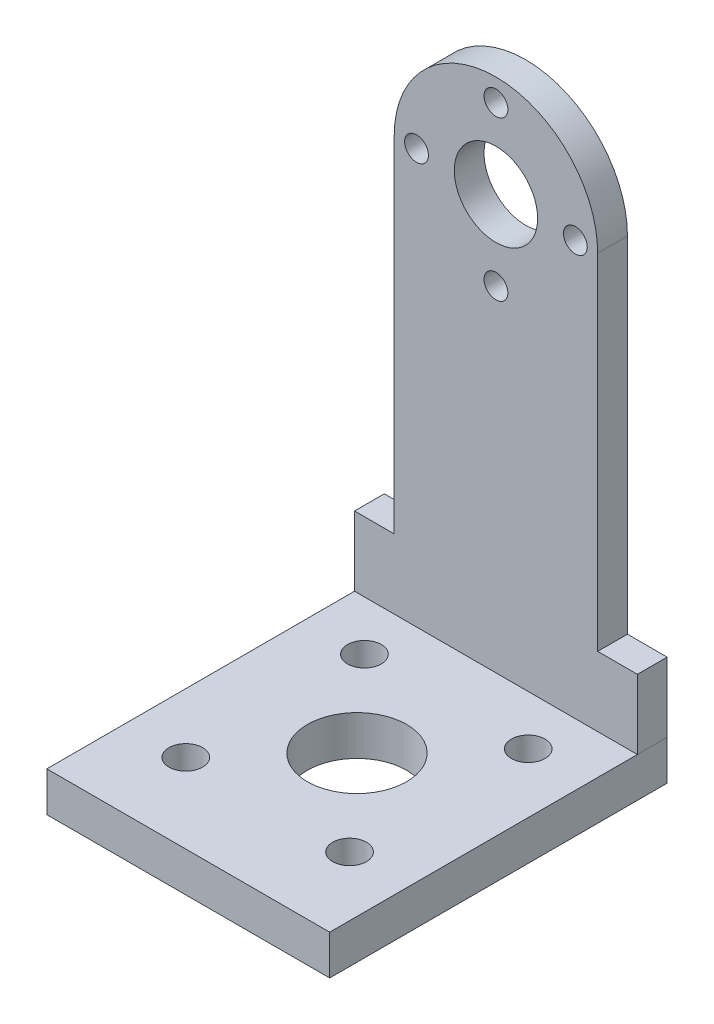
SolidWorks part; units mm, degrees
ref_plane "Front Plane" through (0, 0, 0) normal (0, 0, 1) x (1, 0, 0)
ref_plane "Top Plane" through (0, 0, 0) normal (0, 1, 0) x (1, 0, 0)
ref_plane "Right Plane" through (0, 0, 0) normal (1, 0, 0) x (0, 0, -1)
sketch "Sketch1" plane through (0, 0, 0) normal (0, 0, 1) x (1, 0, 0)
  line L0 (0, 0) -> (0, -100) construction
  line L1 (0, -100) -> (-70, -100) construction
  line L2 (-10.25, -60) -> (-70, -60) construction
  line L4 (-10.25, 0) -> (10.25, 0)
  line L5 (-10.25, 0) -> (-10.25, -60)
  line L7 (10.25, 0) -> (10.25, -60)
  line L8 (-10.25, 0) -> (10.25, 0)
  line L9 (-10.25, 0) -> (-10.25, -100)
  line L10 (-10.25, -100) -> (10.25, -100)
  line L11 (10.25, 0) -> (10.25, -100)
  circle A0 centre (0, 0) radius 10.25
  circle A1 centre (0, 0) radius 8
  circle A2 centre (0, 0) radius 4.2
  circle A3 centre (0, 8) radius 1.2
  circle A4 centre (8, 0) radius 1.2
  circle A5 centre (0, -8) radius 1.2
  circle A6 centre (-8, 0) radius 1.2
  point P16 (0, 0)
  dimension "D1" = 20.5
  dimension "D2" = 16
  dimension "D3" = 8.4
  dimension "D4" = 2.4
  dimension "D6" = 100
  dimension "D7" = 70
  dimension "D8" = 40
  dimension "D5" = 4
extrude "Boss-Extrude1" add sketch "Sketch1" along normal blind 22 and the other way blind 22 contours A0 L5 L7 | A6 L4 A0 A4 A1 A5 | A6 A1 A5 A4 L4 A2 | A6 L4 A2 A4 A1 A3 | A6 A1 A3 A4 L4 A0 region at (8.972, 1.0478, 0) region at (9.725, -0.2292, 0) region at (6.9906, -0.9364, 0) region at (5.5, 0.1769, 0) region at (0, -53.9967, 0)
sketch "Sketch2" plane through (-10.25, 0, 0) normal (-1, 0, 0) x (0, 0, 1)
  line L0 (22, 10.25) -> (-22, 10.25) construction
  line L1 (-19, 10.25) -> (19, 10.25)
  line L2 (-19, 10.25) -> (-19, -9.75)
  line L3 (-19, -9.75) -> (19, -9.75)
  line L4 (19, 10.25) -> (19, -9.75)
  line L5 (22, 0) -> (22, 10.25) construction
  line L6 (-22, 10.25) -> (-22, 0) construction
  dimension "D1" = 3
  dimension "D2" = 3
  dimension "D3" = 20
extrude "Cut-Extrude1" cut sketch "Sketch2" against normal through all
sketch "Sketch3" plane through (0, -9.75, 0) normal (0, 1, 0) x (1, 0, 0)
  line L1 (-10.25, 22) -> (-17.25, 22)
  line L2 (-10.25, 22) -> (-10.25, -22)
  line L3 (-10.25, -22) -> (-17.25, -22)
  line L4 (-17.25, 22) -> (-17.25, -22)
  line L5 (10.25, 22) -> (17.25, 22)
  line L6 (10.25, 22) -> (10.25, -22)
  line L7 (10.25, -22) -> (17.25, -22)
  line L8 (17.25, 22) -> (17.25, -22)
  dimension "D1" = 7
  dimension "D2" = 7
extrude "Boss-Extrude2" add sketch "Sketch3" against normal blind 36
sketch "Sketch5" plane through (-17.25, 0, 0) normal (-1, 0, 0) x (0, 0, 1)
  line L0 (-22, -9.75) -> (22, -9.75) construction
  line L1 (-17, -9.75) -> (17, -9.75)
  line L2 (-17, -9.75) -> (-17, -59.75)
  line L3 (-17, -59.75) -> (17, -59.75)
  line L4 (17, -9.75) -> (17, -59.75)
  line L8 (-19, 0) -> (-19, -9.75) construction
  dimension "D1" = 34
  dimension "D2" = 2
  dimension "D3" = 50
extrude "Cut-Extrude3" cut sketch "Sketch5" against normal through all
sketch "Sketch6" plane through (0, 0, 22) normal (0, 0, 1) x (1, 0, 0)
  line L1 (10.25, -45.75) -> (-10.25, -45.75)
  line L2 (10.25, -45.75) -> (10.25, -100)
  line L3 (10.25, -100) -> (-10.25, -100)
  line L4 (-10.25, -45.75) -> (-10.25, -100)
extrude "Cut-Extrude4" cut sketch "Sketch6" against normal through all
sketch "Sketch20" plane through (0, -45.75, 0) normal (0, -1, 0) x (1, 0, 0)
  line L1 (-17.25, 22) -> (17.25, 22)
  line L2 (-17.25, 22) -> (-17.25, -22)
  line L3 (-17.25, -22) -> (17.25, -22)
  line L4 (17.25, 22) -> (17.25, -22)
  line L5 (-17.25, 17) -> (17.25, 17) construction
  line L6 (17.25, -17) -> (-17.25, -17) construction
  line L8 (-14.25, 17) -> (14.25, 17)
  line L9 (-14.25, 17) -> (-14.25, -17)
  line L10 (-14.25, -17) -> (14.25, -17)
  line L11 (14.25, 17) -> (14.25, -17)
  circle A0 centre (0, 0) radius 5
  circle A2 centre (-8.25, 9) radius 1.7
  circle A3 centre (8.25, 9) radius 1.7
  circle A4 centre (8.25, -9) radius 1.7
  circle A5 centre (-8.25, -9) radius 1.7
  line M7 (-17.25, 17) -> (17.25, 17)
  dimension "D1" = 3
  dimension "D2" = 3
  dimension "D3" = 6
  dimension "D4" = 8
  dimension "D5" = 2
  dimension "D6" = 2
extrude "Boss-Extrude5" add sketch "Sketch20" against normal blind 4 contours L11 L9 L10 A5 A4 A3 A2 A0 M7 region at (0, -45.75, 16.5564)
sketch "Sketch21" plane through (0, 0, -22) normal (0, 0, -1) x (-1, 0, 0)
  line L0 (-17.25, -45.75) -> (17.25, -45.75) construction
  line L1 (-17.25, -9.75) -> (-14.25, -9.75)
  line L2 (-17.25, -9.75) -> (-17.25, -45.75)
  line L3 (-17.25, -45.75) -> (-14.25, -45.75)
  line L4 (-14.25, -9.75) -> (-14.25, -45.75)
  line L6 (17.25, -9.75) -> (14.25, -9.75)
  line L7 (17.25, -9.75) -> (17.25, -45.75)
  line L8 (17.25, -45.75) -> (14.25, -45.75)
  line L9 (14.25, -9.75) -> (14.25, -45.75)
  dimension "D1" = 3
  dimension "D2" = 3
extrude "Cut-Extrude12" cut sketch "Sketch21" against normal through all
sketch "Sketch22" plane through (0, 0, -22) normal (0, 0, -1) x (-1, 0, 0)
  line L0 (-14.25, -45.75) -> (-14.25, -9.75) construction
  line L1 (-10.25, -9.75) -> (-14.25, -9.75)
  line L2 (-10.25, -9.75) -> (-10.25, -34.75)
  line L3 (-10.25, -34.75) -> (-14.25, -34.75)
  line L4 (-14.25, -9.75) -> (-14.25, -34.75)
  line L5 (14.25, -9.75) -> (14.25, -45.75) construction
  line L6 (10.25, -9.75) -> (14.25, -9.75)
  line L7 (10.25, -9.75) -> (10.25, -34.75)
  line L8 (10.25, -34.75) -> (14.25, -34.75)
  line L9 (14.25, -9.75) -> (14.25, -34.75)
  dimension "D1" = 25
extrude "Cut-Extrude14" cut sketch "Sketch22" against normal through all contours L9 L8 L7 L6
sketch "Sketch23" plane through (14.25, 0, 0) normal (1, 0, 0) x (0, 0, -1)
  line L2 (-17, -41.75) -> (-17, 10.25)
  line L3 (-17, 10.25) -> (-22, 10.25)
  line L4 (-22, -41.75) -> (-22, 10.25)
  line L5 (-22, -45.75) -> (-17, -45.75)
  line L6 (-22, -45.75) -> (-22, 10.25)
  line L7 (-22, 10.25) -> (-17, 10.25)
  line L8 (-17, -45.75) -> (-17, 10.25)
  line M5 (-22, -45.75) -> (22, -45.75)
  line M10 (-17, -41.75) -> (-17, -9.75)
  line M11 (-17, -9.75) -> (-22, -9.75)
  line M12 (-22, -9.75) -> (-22, -45.75)
extrude "Cut-Extrude15" cut sketch "Sketch23" against normal through all contours L8 M5 M10 M11 M12 | L4 L2 L3 M11 region at (14.25, -27.75, 19.5) region at (14.25, 0.25, 19.5)
sketch "Sketch24" plane through (0, 0, -17) normal (0, 0, 1) x (1, 0, 0)
  line L1 (14.25, -41.75) -> (-10.25, -41.75)
  line L2 (14.25, -41.75) -> (14.25, -9.75)
  line L3 (14.25, -9.75) -> (-10.25, -9.75)
  line L4 (-10.25, -41.75) -> (-10.25, -9.75)
  line L5 (-14.25, -34.75) -> (-10.25, -34.75)
  line L6 (-14.25, -34.75) -> (-14.25, -41.75)
  line L7 (-14.25, -41.75) -> (-10.25, -41.75)
  line L8 (-10.25, -34.75) -> (-10.25, -41.75)
  line L9 (10.25, -9.75) -> (-10.25, -9.75)
  line L10 (10.25, -9.75) -> (10.25, 0)
  line L11 (10.25, 0) -> (-10.25, 0)
  line L12 (-10.25, -9.75) -> (-10.25, 0)
  line L13 (14.25, -9.75) -> (10.25, -9.75)
  line L14 (14.25, -9.75) -> (14.25, -34.75)
  line L15 (14.25, -34.75) -> (10.25, -34.75)
  line L16 (10.25, -9.75) -> (10.25, -34.75)
  circle A0 centre (0, 0) radius 4.2
  circle A1 centre (0, 8) radius 1.2
  circle A2 centre (8, 0) radius 1.2
  circle A3 centre (0, -8) radius 1.2
  circle A4 centre (-8, 0) radius 1.2
  circle A5 centre (0, 0) radius 4.2
  circle A6 centre (0, 0) radius 10.25
  line M1 (-10.25, -9.75) -> (-10.25, -34.75)
  line M2 (-10.25, -34.75) -> (-14.25, -34.75)
  line M3 (-14.25, -34.75) -> (-14.25, -41.75)
  line M4 (-14.25, -41.75) -> (14.25, -41.75)
  line M5 (14.25, -41.75) -> (14.25, -9.75)
extrude "Boss-Extrude8" add sketch "Sketch24" along normal blind 3 separate body contours A6 L3 L4 L15 L16 M1 M4 M5 | L4 M4 M2 M3 | A6 L12 L3 | A6 L3 L10 | L11 A6 L9 A2 A0 A4 A3 | L11 A6 A4 A0 A2 A1 | L9 A6 region at (0.503, -26.3124, -17) region at (-12.25, -38.25, -17) region at (-8.3587, -7.509, -17) region at (8.3587, -7.509, -17) region at (0, -4.827, -17) region at (0, -9.9504, -17) region at (0, 4.9116, -17)
sketch "Sketch25" plane through (-10.25, 0, 0) normal (-1, 0, 0) x (0, 0, 1)
  line L6 (-17, 10.25) -> (-22, 10.25)
  line L7 (-17, 10.25) -> (-17, -45.75)
  line L8 (-17, -45.75) -> (-22, -45.75)
  line L9 (-22, 10.25) -> (-22, -45.75)
extrude "Cut-Extrude16" cut sketch "Sketch25" against normal through all both and the other way through all
